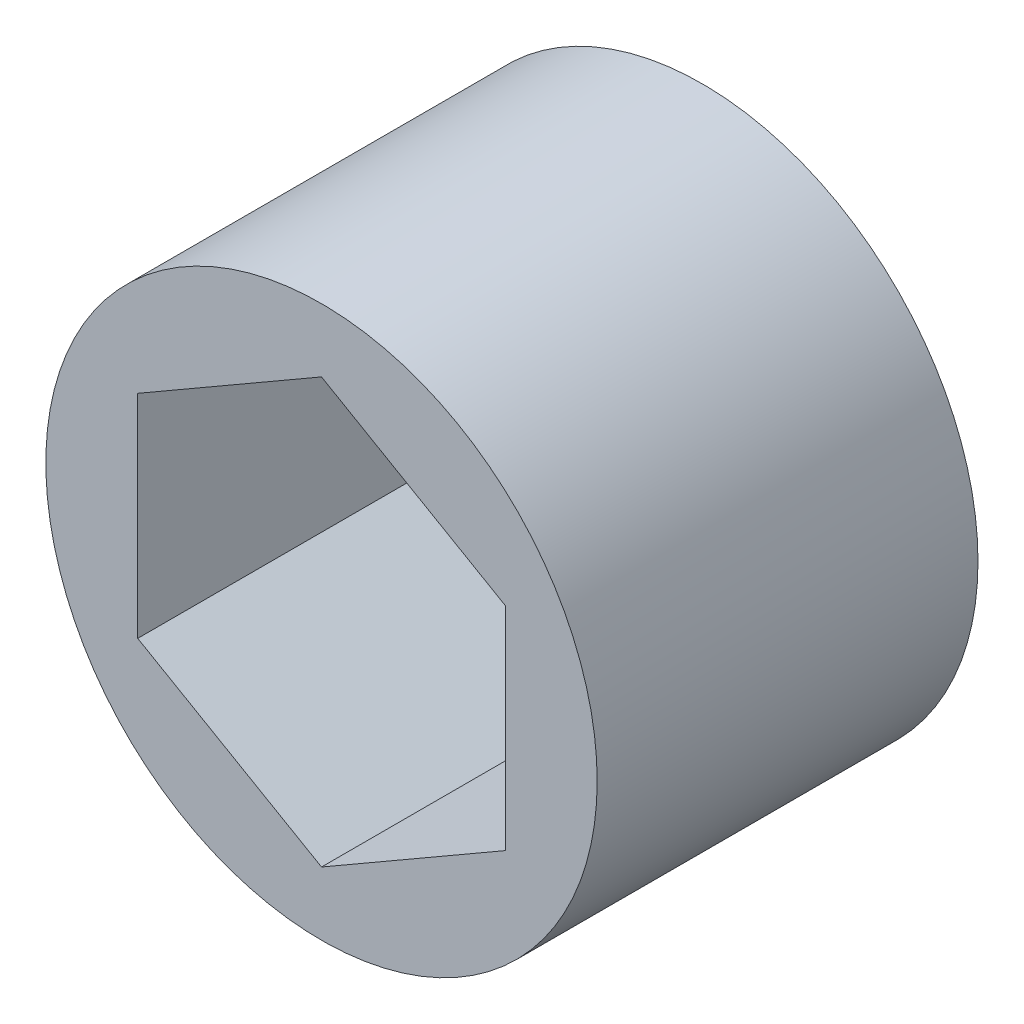
SolidWorks part; units mm, degrees
ref_plane "Front Plane" through (0, 0, 0) normal (0, 0, 1) x (1, 0, 0)
ref_plane "Top Plane" through (0, 0, 0) normal (0, 1, 0) x (1, 0, 0)
ref_plane "Right Plane" through (0, 0, 0) normal (1, 0, 0) x (0, 0, -1)
sketch "Sketch2" plane through (0, 0, 0) normal (0, 0, 1) x (1, 0, 0)
  line L1 (0, 7.3323) -> (-6.35, 3.6662)
  line L2 (-6.35, 3.6662) -> (-6.35, -3.6662)
  line L3 (-6.35, -3.6662) -> (0, -7.3323)
  line L4 (0, -7.3323) -> (6.35, -3.6662)
  line L5 (6.35, -3.6662) -> (6.35, 3.6662)
  line L6 (6.35, 3.6662) -> (0, 7.3323)
  circle A0 centre (0, 0) radius 6.35 construction
  circle A1 centre (0, 0) radius 9.525
  dimension "D1" = 19.05
  dimension ".5" = 12.7
extrude "Boss-Extrude1" add sketch "Sketch2" along normal blind 13.1572
